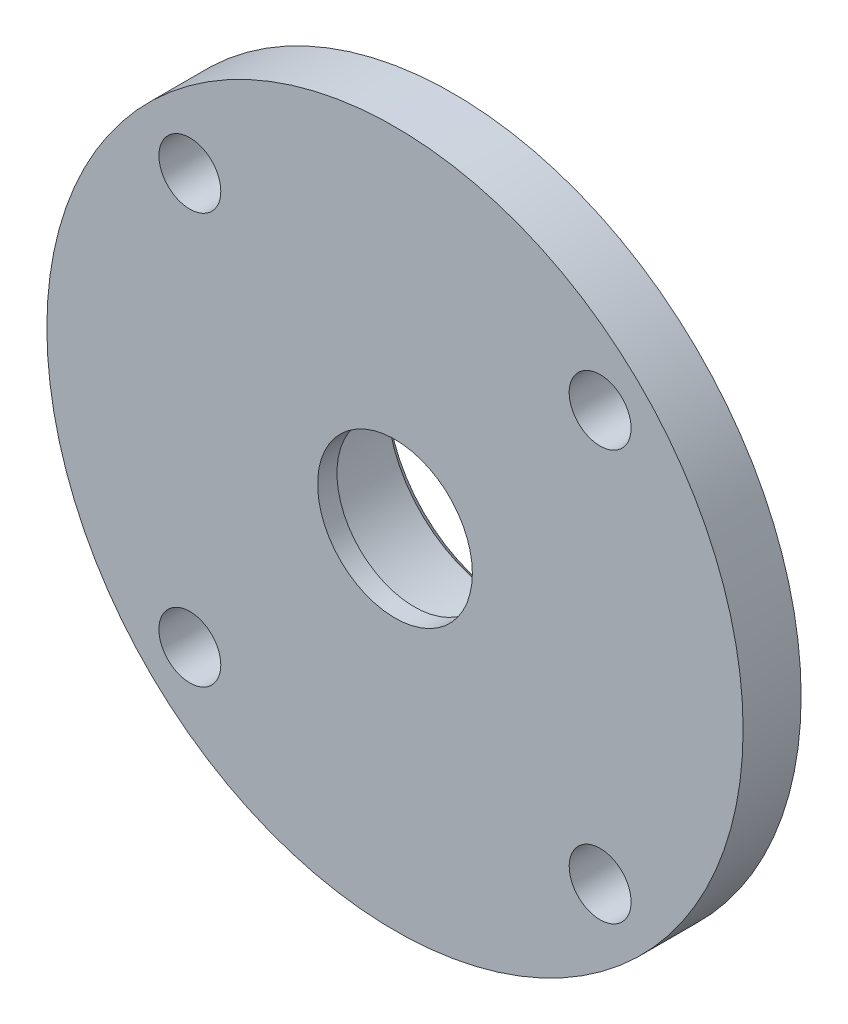
SolidWorks part; units mm, degrees
material "2024 Сплав"
ref_plane "Спереди" through (0, 0, 0) normal (0, 0, 1) x (1, 0, 0)
ref_plane "Сверху" through (0, 0, 0) normal (0, 1, 0) x (1, 0, 0)
ref_plane "Справа" through (0, 0, 0) normal (1, 0, 0) x (0, 0, -1)
sketch "Эскиз1" plane through (0, 0, 0) normal (0, 1, 0) x (1, 0, 0)
  line L0 (-4, 0) -> (-18, 0)
  line L1 (-18, 0) -> (-18, 3)
  line L2 (-18, 3) -> (-9.5, 3)
  line L3 (-9.5, 3) -> (-9.5, 6)
  line L8 (-9.5, 6) -> (-6, 6)
  line L9 (-6, 6) -> (-6, 1)
  line L10 (-6, 1) -> (-4, 1)
  line L11 (-4, 1) -> (-4, 0)
  line L12 (0, 0) -> (0, 50000) construction
  dimension "D1" = 4
  dimension "D2" = 18
  dimension "D3" = 9.5
  dimension "D6" = 1
  dimension "D7" = 6
  dimension "D8" = 6
  dimension "D9" = 3
revolve "Повернуть1" add sketch "Эскиз1" angle 360 about L12
sketch "Эскиз2" plane through (0, 0, 0) normal (0, 0, 1) x (1, 0, 0)
  line L0 (0, 0) -> (18, 0) construction
  circle A0 centre (10.6066, 10.6066) radius 1.6
  circle A1 centre (0, 0) radius 18 construction
  dimension "D2" = 3.2
  dimension "D1" = 45
  dimension "D3" = 15
extrude "Вырез-Вытянуть1" cut sketch "Эскиз2" against normal up to next
pattern_circular "Круговой массив1" count 4 over 360 about axis through (0, 0, 0) along (0, 0, 1) of "Вырез-Вытянуть1"
chamfer "Фаска1" distance 0.4 angle 45 2 edges at (6, 0, -6) (9.5, 0, -6)
